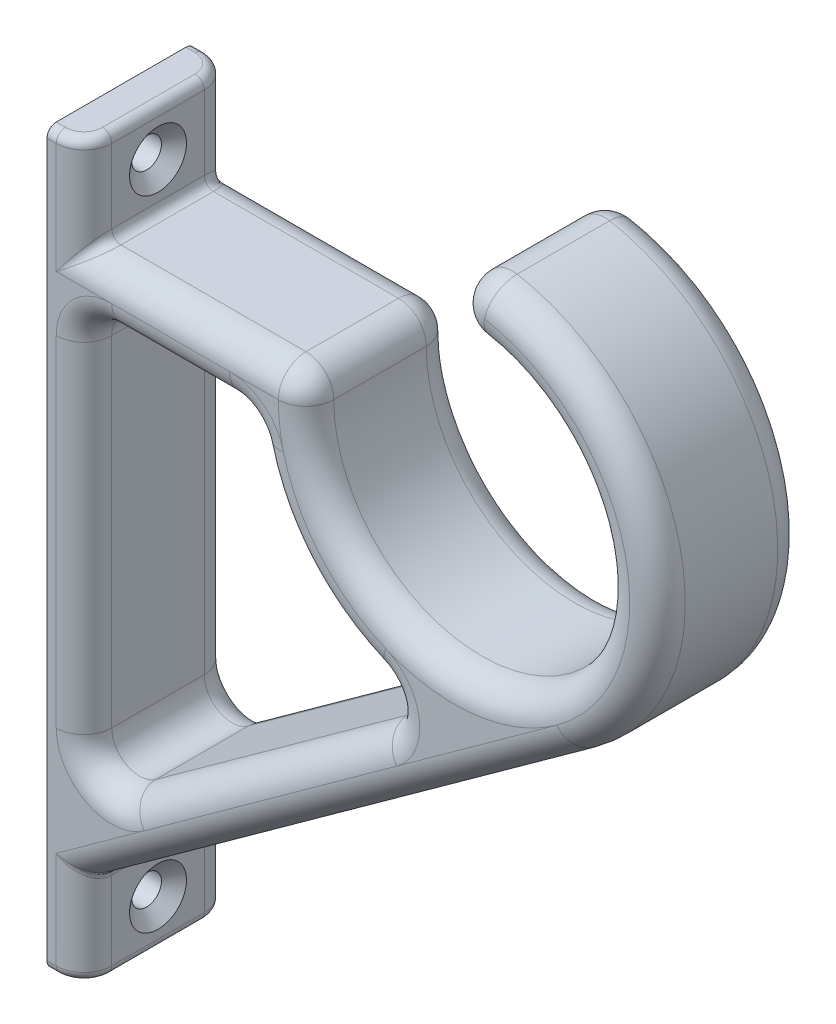
SolidWorks part; units mm, degrees
ref_plane "Front Plane" through (0, 0, 0) normal (0, 0, 1) x (1, 0, 0)
ref_plane "Top Plane" through (0, 0, 0) normal (0, 1, 0) x (1, 0, 0)
ref_plane "Right Plane" through (0, 0, 0) normal (1, 0, 0) x (0, 0, -1)
sketch "Sketch1" plane through (0, 0, 0) normal (0, 0, 1) x (1, 0, 0)
  line L5 (4.4107, 25.0141) -> (6.0647, 34.3944) construction
  line L6 (14.8646, -20.5962) -> (20.4389, -28.3197) construction
  line L7 (-25.4, 0) -> (-69.85, 0) construction
  line L8 (20.4389, -28.3197) -> (-63.5, -88.9)
  line L9 (-63.5, -88.9) -> (-63.5, -104.775)
  line L10 (-63.5, -104.775) -> (-69.85, -104.775)
  line L11 (-69.85, -104.775) -> (-69.85, 0)
  line L13 (-63.5, 4.7625) -> (-30.1625, 4.7625)
  line L14 (-34.5988, -4.7625) -> (-63.5, -4.7625)
  line L15 (-4.5726, -34.6244) -> (-63.5, -77.1534)
  line L16 (-63.5, -4.7625) -> (-63.5, -77.1534)
  line L17 (-69.85, 0) -> (-69.85, 20.6375)
  line L18 (-69.85, 20.6375) -> (-63.5, 20.6375)
  line L19 (-63.5, 20.6375) -> (-63.5, 4.7625)
  arc A0 (4.4107, 25.0141) -> (-25.4, 0) centre (0, 0) cw
  arc A3 (6.0647, 34.3944) -> (20.4389, -28.3197) centre (0, 0) cw
  arc A4 (4.4107, 25.0141) -> (6.0647, 34.3944) centre (5.2377, 29.7043) cw
  arc A6 (-25.4, 0) -> (-30.1625, 4.7625) centre (-30.1625, 0) ccw
  arc A7 (-4.5726, -34.6244) -> (-34.5988, -4.7625) centre (0, 0) cw
  point P16 (30.1355, 1.4781)
  point P22 (4.8183, 34.591)
  dimension "D1" = 25.4
  dimension "D3" = 9.525
  dimension "D2" = 88.9
  dimension "D4" = 69.85
  dimension "D5" = 4.7625
  dimension "D6" = 6.35
  dimension "D7" = 15.875
  dimension "D8" = 100
extrude "Boss-Extrude1" add sketch "Sketch1" along normal mid plane 25.4
fillet "Fillet1" radius 4.7625 28 edges at (-21.5306, -58.6099, 12.7) (34.0423, 7.8026, 12.7) (0.5475, 30.5313, 12.7) (16.3268, -19.4575, 12.7) (-26.7949, 3.3676, 12.7) (-21.5306, -58.6099, -12.7) (34.0423, 7.8026, -12.7) (0.5475, 30.5313, -12.7) (-46.8313, 4.7625, -12.7) (-26.7949, 3.3676, -12.7) (-4.5726, -34.6244, 0) (-34.5988, -4.7625, 0) (-63.5, -4.7625, 0) (-63.5, -77.1534, 0) (-46.8313, 4.7625, 12.7) (16.3268, -19.4575, -12.7) (-24.6279, -24.7634, -12.7) (-63.5, -40.958, 12.7) (-49.0494, -4.7625, -12.7) (-34.0363, -55.8889, -12.7) (-34.0363, -55.8889, 12.7) (-49.0494, -4.7625, 12.7) (-63.5, -40.958, -12.7) (-24.6279, -24.7634, 12.7) (-63.5, -96.8375, -12.7) (-63.5, -96.8375, 12.7) (-63.5, 12.7, -12.7) (-63.5, 12.7, 12.7)
sketch "Sketch2" plane through (-63.5, 0, 0) normal (1, 0, 0) x (0, 0, -1)
  line L0 (-7.9375, 20.6375) -> (7.9375, 4.7625) construction
  line L1 (-7.9375, -104.775) -> (7.9375, -88.9) construction
  point P8 (0, 12.7)
  point P9 (0, -96.8375)
hole_wizard "CSK for #10 Flat Head Machine Screw (100)1" positions "3DSketch1" profile "Sketch3" countersink size "#10" standard "ANSI Inch" end condition up to next
sketch3d "3DSketch1"
  point P0 (-63.5, 12.7, 0)
  point P3 (-63.5, -96.8375, 0)
sketch "Sketch3" plane through (-63.5, 12.7, 0) normal (0, 1, 0) x (0, 0, -1)
  line L0 (0, 0) -> (0, 6.35)
  line L1 (0, 6.35) -> (2.5527, 6.35)
  line L2 (2.5527, 6.35) -> (2.5527, 1.9608)
  line L3 (2.5527, 1.9608) -> (4.8895, 0)
  line L5 (4.8895, 0) -> (0, 0)
  line L6 (-2.5527, 1.9608) -> (-4.8895, 0) construction
  line L11 (0, -6.35) -> (0, 107.95) construction
  dimension "Thru Hole Dia." = 5.1054
  dimension "Thru Hole Depth" = 6.35
  dimension "Near C'Sink Dia." = 9.779
  dimension "Near C'Sink Angle" = 100
fillet "Fillet2" radius 1.5875 16 edges at (-64.8949, 3.3676, 11.3051) (-64.8949, 3.3676, -11.3051) (-64.8949, -88.1865, 11.3051) (-64.8949, -88.1865, -11.3051) (-69.0563, -104.775, 12.7) (-64.8949, -104.775, 11.3051) (-69.0563, -104.775, -12.7) (-64.8949, -104.775, -11.3051) (-69.0563, 20.6375, 12.7) (-64.8949, 20.6375, 11.3051) (-69.0563, 20.6375, -12.7) (-64.8949, 20.6375, -11.3051) (-63.5, 4.7625, 0) (-63.5, -88.9, 0) (-63.5, -104.775, 0) (-63.5, 20.6375, 0)
